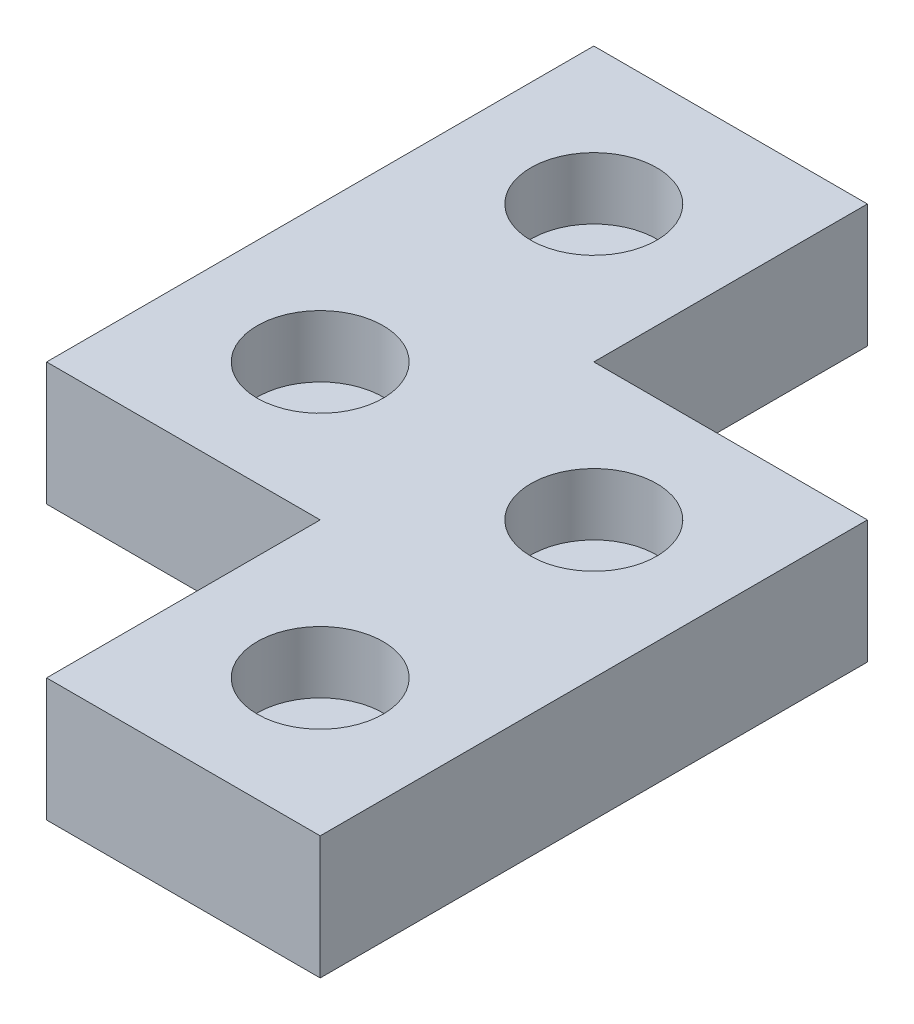
SolidWorks part; units mm, degrees
ref_plane "Front Plane" through (0, 0, 0) normal (0, 0, 1) x (1, 0, 0)
ref_plane "Top Plane" through (0, 0, 0) normal (0, 1, 0) x (1, 0, 0)
ref_plane "Right Plane" through (0, 0, 0) normal (1, 0, 0) x (0, 0, -1)
sketch "Sketch1" plane through (0, 0, 0) normal (0, 1, 0) x (1, 0, 0)
  line L0 (-12.7, 15.597) -> (0, 15.597)
  line L1 (0, 15.597) -> (0, 2.897)
  line L2 (0, 2.897) -> (12.7, 2.897)
  line L3 (12.7, 2.897) -> (12.7, -22.503)
  line L4 (12.7, -22.503) -> (0, -22.503)
  line L5 (0, -22.503) -> (0, -9.803)
  line L6 (0, -9.803) -> (-12.7, -9.803)
  line L7 (-12.7, -9.803) -> (-12.7, 15.597)
  dimension "D1" = 12.7
  dimension "D2" = 25.4
  dimension "D3" = 12.7
  dimension "D4" = 12.7
  dimension "D5" = 25.4
extrude "Boss-Extrude2" add sketch "Sketch1" along normal blind 5.715 contours L7 L0 L1 L2 L3 L4 L5 L6
sketch "Sketch2" plane through (0, 5.715, 0) normal (0, 1, 0) x (1, 0, 0)
  line L0 (0, 15.597) -> (0, 2.897) construction
  line L1 (12.7, -22.503) -> (0, -22.503) construction
  circle A0 centre (-6.35, 9.247) radius 2.921
  circle A1 centre (6.35, -16.153) radius 2.921
  circle A2 centre (-6.35, -3.453) radius 2.921
  circle A3 centre (6.35, -3.453) radius 2.921
  point P8 (0, 0)
  point P9 (0, 0)
  dimension "D1" = 6.35
  dimension "D2" = 12.7
  dimension "D3" = 12.7
  dimension "D4" = 6.35
  dimension "D5" = 12.7
extrude "Cut-Extrude1" cut sketch "Sketch2" against normal blind 2.8702
sketch "Sketch3" plane through (0, 0, 0) normal (0, 1, 0) x (1, 0, 0)
  line L0 (-24.8243, 25.5073) -> (-24.8243, -34.1491) construction
ref_plane "Plane1" through (-24.8243, 0, 0) normal (-1, 0, 0) x (0, 0, 1)
